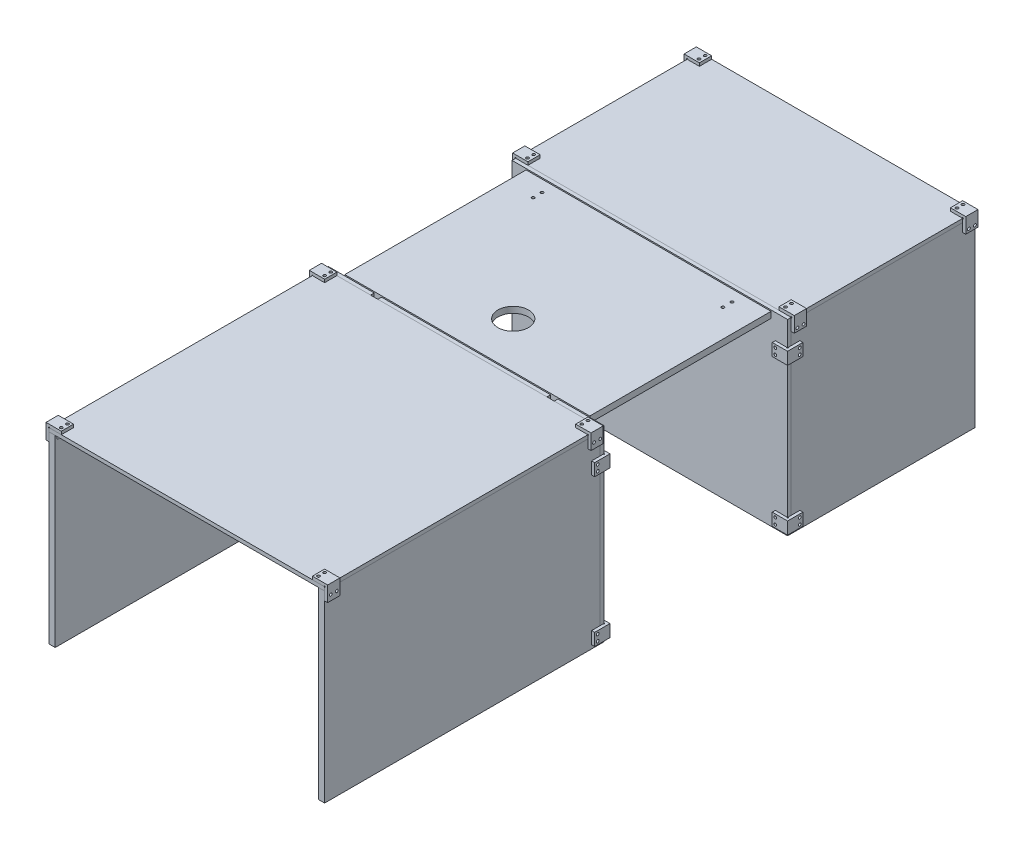
SolidWorks part; units mm, degrees
note: The reader was unsure of these and kept them because the rebuilt part matched: shared geometry of "Sketch1<3>", "Sketch1<4>", "Sketch1<5>", "Sketch3<2>", "Sketch3<3>", "Sketch3<4>", "Sketch5<3>", "Sketch9<3>", "Sketch9<4>", "Sketch9<5>", "Sketch11<2>", "Sketch12<4>".
ref_plane "Front Plane" through (0, 0, 0) normal (0, 0, 1) x (1, 0, 0)
ref_plane "Top Plane" through (0, 0, 0) normal (0, 1, 0) x (1, 0, 0)
ref_plane "Right Plane" through (0, 0, 0) normal (1, 0, 0) x (0, 0, -1)
sketch "Sketch1" plane through (0, 0, 0) normal (1, 0, 0) x (0, 0, -1)
  line L1 (0, 0) -> (450, 0)
  line L2 (0, 0) -> (0, 300)
  line L3 (0, 300) -> (450, 300)
  line L4 (450, 0) -> (450, 300)
  line L5 (762, 0) -> (1062, 0)
  line L6 (762, 0) -> (762, 300)
  line L7 (762, 300) -> (1062, 300)
  line L8 (1062, 0) -> (1062, 300)
  line L9 (0, 300) -> (450, 300)
  line L10 (0, 300) -> (0, 306)
  line L11 (0, 306) -> (450, 306)
  line L12 (450, 300) -> (450, 306)
  line L13 (762, 300) -> (1062, 300)
  line L14 (762, 300) -> (762, 306)
  line L15 (762, 306) -> (1062, 306)
  line L16 (1062, 300) -> (1062, 306)
  line L17 (450, 306) -> (456, 306)
  line L18 (450, 306) -> (450, 0)
  line L19 (450, 0) -> (456, 0)
  line L20 (456, 306) -> (456, 0)
  line L21 (762, 306) -> (756, 306)
  line L22 (762, 306) -> (762, 0)
  line L23 (762, 0) -> (756, 0)
  line L24 (756, 306) -> (756, 0)
  dimension "D1" = 450
  dimension "D2" = 300
  dimension "D3" = 300
  dimension "D4" = 300
  dimension "D5" = 312
  dimension "D6" = 6
  dimension "D7" = 6
  dimension "D8" = 6
  dimension "D9" = 6
extrude "Boss-Extrude1" add sketch "Sketch1" along normal blind 10 contours L1 L4 L3 L2 | L5 L8 L7 L6
extrude "Boss-Extrude2" add sketch "Sketch1<3>" along normal blind 450 separate body contours L3 L12 L11 L10 | L7 L16 L15 L14
sketch "Sketch1<3>" plane through (0, 0, 0) normal (1, 0, 0) x (0, 0, -1) same geometry as "Sketch1"
extrude "Boss-Extrude3" add sketch "Sketch1<4>" against normal blind 10 from surface at 450 separate body contours L1 L4 L3 L2 | L5 L8 L7 L6 starting at face at (450, 303, -225)
sketch "Sketch1<4>" plane through (0, 0, 0) normal (1, 0, 0) x (0, 0, -1) same geometry as "Sketch1"
extrude "Boss-Extrude4" add sketch "Sketch1<5>" along normal up to surface (450 mm away) separate body contours L20 L17 L12 L4 L19 | L21 L24 L23 L6 L14 up to face at (450, 150, -225)
sketch "Sketch1<5>" plane through (0, 0, 0) normal (1, 0, 0) x (0, 0, -1) same geometry as "Sketch1"
sketch3d "3DSketch1"
  line L0 (450, 306, 0) -> (0, 306, 0) construction
  line L1 (450, 306, -450) -> (0, 306, -450) construction
  line L2 (225, 306, 0) -> (225, 306, -450)
  point P0 (225, 306, 0)
  point P1 (225, 306, -450)
sketch "Sketch2" plane through (225, 0, 0) normal (-1, 0, 0) x (0, 0, 1)
  line L0 (-456, 306) -> (-456, 0) construction
  line L1 (-754, 306) -> (-458, 306)
  line L2 (-754, 306) -> (-754, 296)
  line L3 (-754, 296) -> (-458, 296)
  line L4 (-458, 306) -> (-458, 296)
  line L6 (-756, 306) -> (-756, 0) construction
  line L7 (-762, 306) -> (-1062, 306) construction
  dimension "D1" = 10
  dimension "D2" = 2
  dimension "D3" = 2
extrude "Boss-Extrude5" add sketch "Sketch2" along normal blind 200 and the other way blind 200 separate body
sketch "Sketch3" plane through (0, 0, 0) normal (0, 0, 1) x (1, 0, 0)
  line L0 (430, 306) -> (430, 311)
  line L1 (450, 306) -> (0, 306) construction
  line L2 (430, 311) -> (455, 311)
  line L3 (455, 311) -> (455, 286)
  line L4 (455, 286) -> (450, 286)
  line L5 (450, 300) -> (450, 0) construction
  line L6 (450, 286) -> (450, 305)
  line L7 (449, 306) -> (430, 306)
  line L8 (225, 306) -> (225, 0) construction
  line L9 (1, 306) -> (20, 306)
  line L10 (0, 286) -> (0, 305)
  line L11 (-5, 286) -> (0, 286)
  line L12 (-5, 311) -> (-5, 286)
  line L13 (20, 311) -> (-5, 311)
  line L14 (20, 306) -> (20, 311)
  arc A0 (450, 305) -> (449, 306) centre (450, 306) ccw
  arc A1 (0, 305) -> (1, 306) centre (0, 306) cw
  dimension "D5" = 2
  dimension "D1" = 20
  dimension "D2" = 5
  dimension "D3" = 5
  dimension "D4" = 20
extrude "Boss-Extrude6" add sketch "Sketch3" against normal blind 20 separate body
extrude "Boss-Extrude7" add sketch "Sketch3<2>" along normal blind 20 from vertex at -430 separate body
sketch "Sketch3<2>" plane through (0, 0, 0) normal (0, 0, 1) x (1, 0, 0) same geometry as "Sketch3"
extrude "Boss-Extrude8" add sketch "Sketch3<3>" along normal blind 20 from vertex at -1062 separate body starting at point (450, 306, -1062)
sketch "Sketch3<3>" plane through (0, 0, 0) normal (0, 0, 1) x (1, 0, 0) same geometry as "Sketch3"
extrude "Boss-Extrude9" add sketch "Sketch3<4>" against normal blind 20 from vertex at -762 separate body starting at point (450, 306, -762)
sketch "Sketch3<4>" plane through (0, 0, 0) normal (0, 0, 1) x (1, 0, 0) same geometry as "Sketch3"
sketch "Sketch5" plane through (0, 306, 0) normal (0, 1, 0) x (1, 0, 0)
  line L0 (450, 756) -> (0, 756) construction
  line L1 (430, 756) -> (449, 756)
  line L2 (430, 756) -> (430, 751)
  line L3 (430, 751) -> (455, 751)
  line L5 (225, 1062) -> (225, 762) construction
  line L7 (455, 751) -> (455, 776)
  line L8 (455, 776) -> (450, 776)
  line L9 (450, 757) -> (450, 776)
  line L10 (450, 1062) -> (0, 1062) construction
  line L11 (450, 762) -> (0, 762) construction
  line L20 (225, 756) -> (225, 456) construction
  line L22 (450, 456) -> (0, 456) construction
  line L23 (0, 606) -> (450, 606) construction
  line L28 (450, 756) -> (450, 762) construction
  line L42 (450, 762) -> (450, 1062) construction
  line L47 (0, 757) -> (0, 776)
  line L54 (-5, 776) -> (0, 776)
  line L58 (-5, 751) -> (-5, 776)
  line L59 (20, 751) -> (-5, 751)
  line L60 (20, 756) -> (20, 751)
  line L61 (20, 756) -> (1, 756)
  line L62 (20, 456) -> (1, 456)
  line L63 (20, 456) -> (20, 461)
  line L64 (20, 461) -> (-5, 461)
  line L65 (-5, 461) -> (-5, 436)
  line L66 (-5, 436) -> (0, 436)
  line L67 (0, 455) -> (0, 436)
  line L68 (450, 455) -> (450, 436)
  line L69 (455, 436) -> (450, 436)
  line L70 (455, 461) -> (455, 436)
  line L71 (430, 461) -> (455, 461)
  line L72 (430, 456) -> (430, 461)
  line L73 (430, 456) -> (449, 456)
  arc A7 (449, 756) -> (450, 757) centre (450, 756) ccw
  arc A8 (1, 756) -> (0, 757) centre (0, 756) cw
  arc A9 (1, 456) -> (0, 455) centre (0, 456) ccw
  arc A10 (449, 456) -> (450, 455) centre (450, 456) cw
  point P8 (225, 606)
  dimension "D1" = 20
  dimension "D5" = 1
  dimension "D2" = 5
  dimension "D3" = 5
  dimension "D4" = 20
extrude "Boss-Extrude10" add sketch "Sketch5" against normal blind 20 from offset 40 separate body offset against normal yes
extrude "Boss-Extrude11" add sketch "Sketch5<3>" along normal blind 20 from offset 300 separate body offset against normal yes
sketch "Sketch5<3>" plane through (0, 306, 0) normal (0, 1, 0) x (1, 0, 0) same geometry as "Sketch5"
sketch "Sketch6" plane through (0, 0, 0) normal (-1, 0, 0) x (0, 0, 1)
  line L0 (-762, 0) -> (-450, 0) construction
  line L1 (-606, 0) -> (-606, 265) construction
  circle A0 centre (-445, 295) radius 5 construction
  circle A1 centre (-435, 295) radius 5 construction
  circle A2 centre (-445, 295) radius 2.25
  circle A3 centre (-435, 295) radius 2.25
  circle A4 centre (-5, 295) radius 2.25
  circle A5 centre (-5, 295) radius 5 construction
  circle A6 centre (-15, 295) radius 2.25
  circle A7 centre (-15, 295) radius 5 construction
  circle A8 centre (-777.0216, 291.1065) radius 5 construction
  circle A9 centre (-767.1075, 291.1065) radius 2.25
  circle A10 centre (-767.1075, 291.1065) radius 5 construction
  circle A11 centre (-777.0216, 291.1065) radius 2.25
  circle A12 centre (-1056.9965, 291.1065) radius 5 construction
  circle A13 centre (-1047.1627, 291.1065) radius 5 construction
  circle A14 centre (-1047.1627, 291.1065) radius 2.25
  circle A15 centre (-1056.9965, 291.1065) radius 2.25
  circle A16 centre (-441.0707, 260.8731) radius 2.25
  circle A17 centre (-441.0707, 251.2302) radius 5 construction
  circle A18 centre (-441.0707, 260.8731) radius 5 construction
  circle A19 centre (-441.0707, 251.2302) radius 2.25
  circle A20 centre (-441.0707, 11.0034) radius 5 construction
  circle A21 centre (-441.0707, 20.9795) radius 2.25
  circle A22 centre (-441.0707, 11.0034) radius 2.25
  circle A23 centre (-441.0707, 20.9795) radius 5 construction
  circle A24 centre (-770.9293, 20.9795) radius 5 construction
  circle A25 centre (-770.9293, 11.0034) radius 5 construction
  circle A26 centre (-770.9293, 260.8731) radius 5 construction
  circle A27 centre (-770.9293, 251.2302) radius 5 construction
  circle A28 centre (-770.9293, 11.0034) radius 2.25
  circle A29 centre (-770.9293, 20.9795) radius 2.25
  circle A30 centre (-770.9293, 251.2302) radius 2.25
  circle A31 centre (-770.9293, 260.8731) radius 2.25
extrude "Cut-Extrude1" cut sketch "Sketch6" against normal through all both and the other way through all
sketch "Sketch7" plane through (0, 306, 0) normal (0, 1, 0) x (1, 0, 0)
  line L0 (10, 450) -> (10, 430) construction
  line L1 (20, 782) -> (-5, 782) construction
  line L2 (0, 912) -> (450, 912) construction
  line L3 (10, 20) -> (10, 0) construction
  line L4 (9.4479, 782) -> (9.4479, 762) construction
  line L5 (450, 762) -> (0, 762) construction
  line L6 (0, 762) -> (0, 1062) construction
  line L7 (450, 1062) -> (450, 762) construction
  line L8 (225, 1062) -> (225, 762) construction
  line L9 (450, 1062) -> (0, 1062) construction
  line L10 (450, 762) -> (0, 762) construction
  line L11 (440, 20) -> (440, 0) construction
  line L12 (440, 450) -> (440, 430) construction
  circle A1 centre (14.4479, 777) radius 5 construction
  circle A2 centre (14.4479, 767) radius 5 construction
  circle A3 centre (14.4479, 777) radius 2.25
  circle A4 centre (14.4479, 767) radius 2.25
  circle A5 centre (435.5521, 767) radius 5 construction
  circle A6 centre (435.5521, 777) radius 5 construction
  circle A7 centre (435.5521, 767) radius 2.25
  circle A8 centre (435.5521, 777) radius 2.25
  circle A9 centre (435.5521, 1047) radius 5 construction
  circle A10 centre (435.5521, 1057) radius 5 construction
  circle A11 centre (14.4479, 1057) radius 5 construction
  circle A12 centre (14.4479, 1047) radius 5 construction
  circle A13 centre (435.5521, 1047) radius 2.25
  circle A14 centre (435.5521, 1057) radius 2.25
  circle A15 centre (14.4479, 1057) radius 2.25
  circle A16 centre (14.4479, 1047) radius 2.25
  circle A17 centre (15, 445) radius 5 construction
  circle A18 centre (15, 445) radius 2.25
  circle A19 centre (15, 435) radius 5 construction
  circle A20 centre (15, 435) radius 2.25
  circle A21 centre (15, 5) radius 2.25
  circle A22 centre (15, 15) radius 5 construction
  circle A23 centre (15, 15) radius 2.25
  circle A24 centre (15, 5) radius 5 construction
  circle A25 centre (435, 5) radius 5 construction
  circle A26 centre (435, 15) radius 5 construction
  circle A27 centre (435, 435) radius 5 construction
  circle A28 centre (435, 445) radius 5 construction
  circle A29 centre (435, 15) radius 2.25
  circle A30 centre (435, 5) radius 2.25
  circle A31 centre (435, 435) radius 2.25
  circle A32 centre (435, 445) radius 2.25
extrude "Cut-Extrude2" cut sketch "Sketch7" against normal through all both and the other way through all
sketch "Sketch8" plane through (0, 0, -456) normal (0, 0, -1) x (-1, 0, 0)
  line L0 (-225, 306) -> (-225, 0) construction
  line L1 (-430, 246) -> (-430, 26) construction
  line L2 (-430, 136) -> (-15, 136) construction
  circle A0 centre (-435, 261.0106) radius 5 construction
  circle A1 centre (-435, 251.0171) radius 5 construction
  circle A2 centre (-435, 261.0106) radius 2.25
  circle A3 centre (-435, 251.0171) radius 2.25
  circle A4 centre (-15, 251.0171) radius 5 construction
  circle A5 centre (-15, 261.0106) radius 5 construction
  circle A6 centre (-15, 251.0171) radius 2.25
  circle A7 centre (-15, 261.0106) radius 2.25
  circle A8 centre (-15, 10.9894) radius 5 construction
  circle A9 centre (-15, 20.9829) radius 5 construction
  circle A10 centre (-435, 20.9829) radius 5 construction
  circle A11 centre (-435, 10.9894) radius 5 construction
  circle A12 centre (-15, 10.9894) radius 2.25
  circle A13 centre (-15, 20.9829) radius 2.25
  circle A14 centre (-435, 20.9829) radius 2.25
  circle A15 centre (-435, 10.9894) radius 2.25
extrude "Cut-Extrude3" cut sketch "Sketch8" against normal through all both and the other way through all
sketch "Sketch9" plane through (225, 0, 0) normal (-1, 0, 0) x (0, 0, 1)
  line L0 (-754, 296) -> (-458, 296) construction
  line L1 (-756, 0) -> (-756, 306) construction
  line L2 (-715.4988, 296) -> (-715.4988, 291)
  line L3 (-715.4988, 291) -> (-744.378, 291)
  line L4 (-748.9289, 293.9289) -> (-748.9289, 296)
  line L5 (-748.9289, 296) -> (-715.4988, 296)
  line L6 (-756, 296) -> (-727.9977, 267.9977) construction
  line L7 (-756, 288.9289) -> (-756, 255.4988)
  line L8 (-753.9289, 288.9289) -> (-756, 288.9289)
  line L9 (-751, 255.4988) -> (-751, 284.378)
  line L10 (-756, 255.4988) -> (-751, 255.4988)
  line L11 (-756, 258.7606) -> (-756, 263.2606) construction
  circle A0 centre (-748.9289, 288.9289) radius 7.0711 construction
  circle A1 centre (-748.9289, 288.9289) radius 3.15
  circle A2 centre (-748.9289, 288.9289) radius 5
  dimension "D1" = 5
  dimension "D2" = 10
  dimension "D3" = 10
extrude "Boss-Extrude12" add sketch "Sketch9" against normal blind 10 from offset 150 separate body contours A2 L8 L7 L10 L9 | A2 A1
extrude "Boss-Extrude13" add sketch "Sketch9<3>" along normal blind 10 from offset 150 separate body contours A2 A1 | A2 L3 L2 L5 L4
sketch "Sketch9<3>" plane through (225, 0, 0) normal (-1, 0, 0) x (0, 0, 1) same geometry as "Sketch9"
extrude "Boss-Extrude14" add sketch "Sketch9<4>" along normal blind 10 from offset 150 separate body contours A2 L8 L7 L10 L9 | A2 A1 offset against normal yes
sketch "Sketch9<4>" plane through (225, 0, 0) normal (-1, 0, 0) x (0, 0, 1) same geometry as "Sketch9"
extrude "Boss-Extrude15" add sketch "Sketch9<5>" against normal blind 10 from offset 150 separate body contours A2 L3 L2 L5 L4 | A2 A1 offset against normal yes
sketch "Sketch9<5>" plane through (225, 0, 0) normal (-1, 0, 0) x (0, 0, 1) same geometry as "Sketch9"
fillet "Fillet1" radius 10 2 edges at (70, 293.9289, -748.9289) (70, 291, -744.378)
fillet "Fillet2" radius 10 2 edges at (80, 288.9289, -753.9289) (80, 284.378, -751)
fillet "Fillet3" radius 10 2 edges at (370, 288.9289, -753.9289) (370, 284.378, -751)
fillet "Fillet4" radius 10 2 edges at (380, 293.9289, -748.9289) (380, 291, -744.378)
sketch "Sketch10" plane through (225, 0, 0) normal (-1, 0, 0) x (0, 0, 1)
  line L4 (-756, 258.7606) -> (-756, 263.2606) construction
  line L5 (-748.2679, 290.8038) -> (-726.7234, 253.4876)
  line L7 (-744.8038, 292.8038) -> (-722.3933, 253.9876)
  line L10 (-728.4555, 250.4876) -> (-749, 250.4876)
  line L12 (-726.7234, 246.4876) -> (-749, 246.4876)
  line L16 (-756, 289.8038) -> (-756, 253.4876)
  line L18 (-752, 289.8038) -> (-752, 253.4876)
  arc A0 (-722.3933, 253.9876) -> (-726.7234, 246.4876) centre (-726.7234, 251.4876) cw
  arc A1 (-726.7234, 253.4876) -> (-728.4555, 250.4876) centre (-728.4555, 252.4876) cw
  arc A2 (-756, 289.8038) -> (-744.8038, 292.8038) centre (-750, 289.8038) cw
  arc A3 (-748.2679, 290.8038) -> (-752, 289.8038) centre (-750, 289.8038) ccw
  arc A4 (-756, 253.4876) -> (-749, 246.4876) centre (-749, 253.4876) ccw
  arc A5 (-752, 253.4876) -> (-749, 250.4876) centre (-749, 253.4876) ccw
  dimension "D4" = 5
  dimension "D5" = 2
  dimension "D6" = 6
  dimension "D7" = 2
  dimension "D8" = 7
  dimension "D9" = 3
  dimension "D1" = 4
  dimension "D2" = 4
  dimension "D3" = 4
extrude "Boss-Extrude16" add sketch "Sketch10" along normal blind 10 and the other way blind 10 separate body
sketch "Sketch11" plane through (225, 0, 0) normal (-1, 0, 0) x (0, 0, 1)
  line L0 (-450, 0) -> (-450, 300) construction
  line L1 (-456, 306) -> (-450, 306)
  line L2 (-456, 306) -> (-456, 276)
  line L3 (-456, 276) -> (-450, 276)
  line L4 (-450, 306) -> (-450, 276)
  dimension "D1" = 30
extrude "Cut-Extrude4" cut sketch "Sketch11" against normal blind 12 from offset 150
extrude "Cut-Extrude5" cut sketch "Sketch11<2>" along normal blind 12 from offset 150 offset against normal yes
sketch "Sketch11<2>" plane through (225, 0, 0) normal (-1, 0, 0) x (0, 0, 1) same geometry as "Sketch11"
sketch "Sketch12" plane through (225, 0, 0) normal (-1, 0, 0) x (0, 0, 1)
  line L1 (-754, 296) -> (-458, 296) construction
  line L2 (-456, 306) -> (-456, 276) construction
  line L3 (-456, 306) -> (-456, 0) construction
  line L4 (-465, 296) -> (-456, 276)
  line L5 (-448.5, 276) -> (-456, 276)
  line L7 (-448.5, 276) -> (-450.4873, 287.6776)
  line L10 (-450, 216) -> (-445, 216)
  line L12 (-445, 216) -> (-445, 236)
  line L14 (-445, 236) -> (-446.5, 236)
  line L15 (-448.5, 238) -> (-448.5, 276)
  line L16 (-450, 276) -> (-450, 216)
  line L17 (-450, 0) -> (-450, 306) construction
  line L18 (-460.3602, 293) -> (-460.3455, 293)
  line L19 (-453.4447, 287.1743) -> (-452.0537, 279)
  line L20 (-452.0537, 279) -> (-454.0602, 279)
  line L21 (-454.0602, 279) -> (-460.3602, 293)
  line L22 (-465, 296) -> (-460.3455, 296)
  line L23 (-458, 296) -> (-458, 306) construction
  arc A1 (-450.4873, 287.6776) -> (-460.3455, 296) centre (-460.3455, 286) ccw
  arc A2 (-453.4447, 287.1743) -> (-460.3455, 293) centre (-460.3455, 286) ccw
  arc A3 (-448.5, 238) -> (-446.5, 236) centre (-446.5, 238) ccw
  point P29 (-453.057, 279)
  dimension "D1" = 10
  dimension "D5" = 7
  dimension "D11" = 2
  dimension "D2" = 5
  dimension "D3" = 1.5
  dimension "D4" = 3
  dimension "D6" = 3
  dimension "D7" = 3
  dimension "D8" = 30
  dimension "D9" = 3
  dimension "D10" = 20
  dimension "D12" = 40
  dimension "D13" = 7
extrude "Boss-Extrude17" add sketch "Sketch12" along normal blind 10 from offset 139 separate body contours A1 L2 A2 L19 L20 L21 L5 L7 | L2 A1 L22 L4 L21 L18 A2 | A3 L15 L5 L16 L10 L12 L14
extrude "Boss-Extrude18" add sketch "Sketch12<4>" against normal blind 10 from offset 139 separate body contours A3 L15 L5 L16 L10 L12 L14 | A1 L2 A2 L19 L20 L21 L5 L7 | L2 A1 L22 L4 L21 L18 A2 offset against normal yes
sketch "Sketch12<4>" plane through (225, 0, 0) normal (-1, 0, 0) x (0, 0, 1) same geometry as "Sketch12"
sketch "Sketch13" plane through (0, 0, -445) normal (0, 0, 1) x (1, 0, 0)
  line L0 (225, 300) -> (225, 0) construction
  line L1 (450, 300) -> (0, 300) construction
  line L2 (450, 0) -> (0, 0) construction
  circle A0 centre (369, 231.0113) radius 5 construction
  circle A1 centre (369, 221.1869) radius 5 construction
  circle A2 centre (369, 231.0113) radius 2.25
  circle A3 centre (369, 221.1869) radius 2.25
  circle A4 centre (81, 221.1869) radius 5 construction
  circle A5 centre (81, 231.0113) radius 5 construction
  circle A6 centre (81, 221.1869) radius 2.25
  circle A7 centre (81, 231.0113) radius 2.25
extrude "Cut-Extrude6" cut sketch "Sketch13" against normal through all contours A7 | A6 | A3 | A2
sketch "Sketch14" plane through (0, 291, 0) normal (0, -1, 0) x (1, 0, 0)
  line L0 (225, -721.7234) -> (225, -573.0074) construction
  line L1 (235, -721.7234) -> (215, -721.7234) construction
  circle A0 centre (380, -720.4988) radius 5 construction
  circle A1 centre (380, -735.1958) radius 5 construction
  circle A2 centre (380, -720.4988) radius 2.25
  circle A3 centre (380, -735.1958) radius 2.25
  circle A4 centre (70, -735.1958) radius 5 construction
  circle A5 centre (70, -720.4988) radius 5 construction
  circle A6 centre (70, -735.1958) radius 2.25
  circle A7 centre (70, -720.4988) radius 2.25
extrude "Cut-Extrude7" cut sketch "Sketch14" against normal through all both and the other way through all contours A7 | A6 | A2 | A3
sketch "Sketch15" plane through (0, 0, -756) normal (0, 0, -1) x (-1, 0, 0)
  line L0 (-225, 289.8038) -> (-225, 183.0531) construction
  line L1 (-235, 289.8038) -> (-215, 289.8038) construction
  circle A2 centre (-370, 260.4988) radius 5 construction
  circle A3 centre (-370, 270.4988) radius 5 construction
  circle A4 centre (-370, 270.4988) radius 2.25
  circle A5 centre (-370, 260.4988) radius 2.25
  circle A6 centre (-80, 270.4988) radius 5 construction
  circle A7 centre (-80, 260.4988) radius 5 construction
  circle A8 centre (-80, 260.4988) radius 2.25
  circle A9 centre (-80, 270.4988) radius 2.25
  circle A10 centre (-225, 279.2679) radius 10 construction
  circle A11 centre (-225, 263.4876) radius 10 construction
  circle A12 centre (-225, 279.2679) radius 2.25
  circle A13 centre (-225, 263.4876) radius 2.25
extrude "Cut-Extrude8" cut sketch "Sketch15" against normal blind 10 and the other way blind 20 contours A4 | A5 | A12 | A13 | A8 | A9
sketch "Sketch16" plane through (0, 306, 0) normal (0, 1, 0) x (1, 0, 0)
  line L0 (225, 458) -> (225, 533) construction
  line L1 (425, 458) -> (25, 458) construction
  circle A0 centre (225, 533) radius 25
  dimension "D1" = 75
extrude "Cut-Extrude9" cut sketch "Sketch16" against normal blind 10
